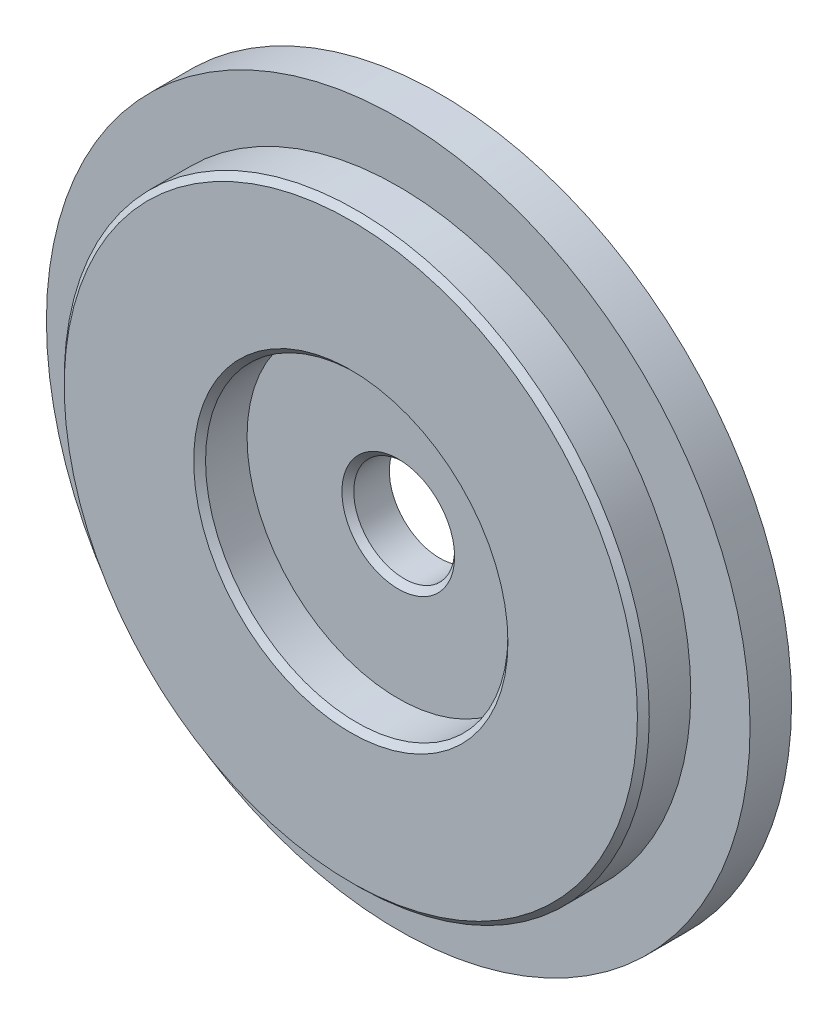
SolidWorks part; units mm, degrees
material "PA 类型 6"
ref_plane "前视基准面" through (0, 0, 0) normal (0, 0, 1) x (1, 0, 0)
ref_plane "上视基准面" through (0, 0, 0) normal (0, 1, 0) x (1, 0, 0)
ref_plane "右视基准面" through (0, 0, 0) normal (1, 0, 0) x (0, 0, -1)
sketch "草图1" plane through (0, 0, 0) normal (0, 0, 1) x (1, 0, 0)
  circle A0 centre (0, 0) radius 17.8
extrude "凸台-拉伸1" add sketch "草图1" along normal blind 2.1
sketch "草图2" plane through (0, 0, 0) normal (0, 0, 1) x (1, 0, 0)
  circle A0 centre (0, 0) radius 14.8
  circle A1 centre (0, 0) radius 7.65
extrude "凸台-拉伸2" add sketch "草图2" along normal blind 4.5
sketch "草图3" plane through (0, 0, 0) normal (0, 0, 1) x (1, 0, 0)
  circle A0 centre (0, 0) radius 2.55
extrude "切除-拉伸1" cut sketch "草图3" along normal up to next
chamfer "倒角1" distance 0.3 angle 45 3 edges at (7.65, 0, 4.5) (2.55, 0, 2.1) (14.8, 0, 4.5)
